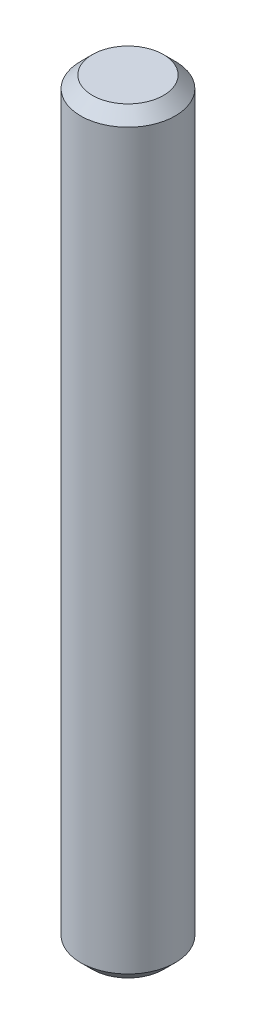
SolidWorks part; units mm, degrees
ref_plane "Front Plane" through (0, 0, 0) normal (0, 0, 1) x (1, 0, 0)
ref_plane "Top Plane" through (0, 0, 0) normal (0, 1, 0) x (1, 0, 0)
ref_plane "Right Plane" through (0, 0, 0) normal (1, 0, 0) x (0, 0, -1)
sketch "Sketch1" plane through (0, 0, 0) normal (0, 1, 0) x (1, 0, 0)
  circle A0 centre (0, 0) radius 1.5875
  dimension "D1" = 3.175
extrude "Boss-Extrude1" add sketch "Sketch1" along normal blind 25.4
chamfer "Chamfer1" distance 0.3969 angle 45 2 edges at (0, 0, 1.5875) (0, 25.4, 1.5875)
